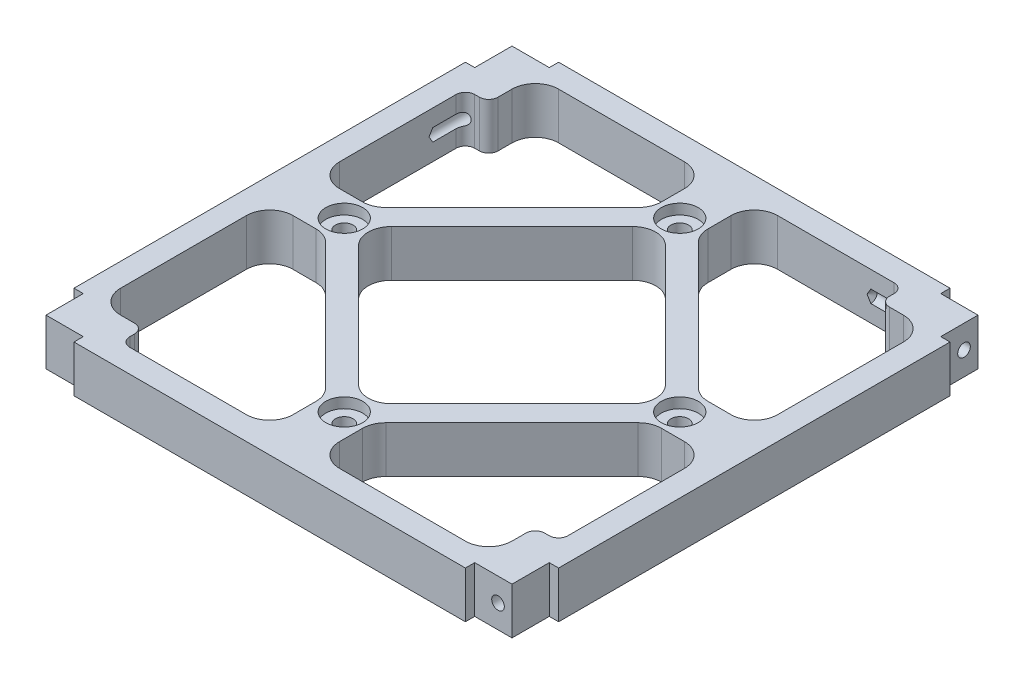
SolidWorks part; units mm, degrees
ref_plane "Front Plane" through (0, 0, 0) normal (0, 0, 1) x (1, 0, 0)
ref_plane "Top Plane" through (0, 0, 0) normal (0, 1, 0) x (1, 0, 0)
ref_plane "Right Plane" through (0, 0, 0) normal (1, 0, 0) x (0, 0, -1)
sketch "Sketch1" plane through (0, 0, 0) normal (0, 1, 0) x (1, 0, 0)
  line L0 (-42, 47) -> (-42, 37)
  line L1 (-52, 52) -> (52, 52)
  line L2 (-52, 52) -> (-52, -52)
  line L3 (-52, -52) -> (52, -52)
  line L4 (52, 52) -> (52, -52)
  line L5 (-47, 5) -> (-35, 5)
  line L6 (-35, 5) -> (-5, 35)
  line L7 (-5, 35) -> (-5, 47)
  line L8 (-5, 47) -> (-42, 47)
  line L9 (0, 0) -> (0, 76.3292) construction
  line L10 (0, 0) -> (-78.8537, 0) construction
  line L11 (0, 0) -> (-66.7994, 66.7994) construction
  line L12 (-32.9289, 0) -> (0, 32.9289)
  line L13 (0, 32.9289) -> (32.9289, 0)
  line L14 (32.9289, 0) -> (0, -32.9289)
  line L15 (0, -32.9289) -> (-32.9289, 0)
  line L16 (5, 47) -> (5, 35)
  line L17 (37, 47) -> (5, 47)
  line L18 (37, 42) -> (37, 47)
  line L19 (47, 42) -> (37, 42)
  line L20 (47, 5) -> (47, 42)
  line L21 (35, 5) -> (47, 5)
  line L22 (5, 35) -> (35, 5)
  line L23 (47, -5) -> (35, -5)
  line L24 (47, -37) -> (47, -5)
  line L25 (42, -37) -> (47, -37)
  line L26 (42, -47) -> (42, -37)
  line L27 (5, -47) -> (42, -47)
  line L28 (5, -35) -> (5, -47)
  line L29 (35, -5) -> (5, -35)
  line L30 (-5, -47) -> (-5, -35)
  line L31 (-42, 37) -> (-47, 37)
  line L32 (-47, 37) -> (-47, 5)
  line L33 (-37, -47) -> (-5, -47)
  line L34 (-37, -42) -> (-37, -47)
  line L35 (-47, -42) -> (-37, -42)
  line L36 (-47, -5) -> (-47, -42)
  line L37 (-35, -5) -> (-47, -5)
  line L38 (-5, -35) -> (-35, -5)
  point P36 (0.1996, 0.1996)
  point P45 (0, 0)
  dimension "D1" = 104
  dimension "D2" = 5
  dimension "D3" = 5
  dimension "D4" = 5
  dimension "D5" = 5
  dimension "D6" = 5
  dimension "D7" = 12
  dimension "D8" = 10
  dimension "D9" = 10
  dimension "D10" = 4
extrude "Boss-Extrude1" add sketch "Sketch1" along normal blind 10
fillet "Fillet1" radius 5 24 edges at (32.9289, 5, 0) (0, 5, 32.9289) (-32.9289, 5, 0) (0, 5, -32.9289) (-5, 5, -47) (-5, 5, -35) (-35, 5, -5) (-47, 5, 42) (-47, 5, 5) (-35, 5, 5) (-5, 5, 35) (-5, 5, 47) (42, 5, 47) (47, 5, 5) (35, 5, 5) (5, 5, 35) (5, 5, 47) (47, 5, -42) (47, 5, -5) (35, 5, -5) (5, 5, -35) (5, 5, -47) (-42, 5, -47) (-47, 5, -5)
sketch "Sketch2" plane through (0, 10, 0) normal (0, 1, 0) x (1, 0, 0)
  line L0 (-52, 52) -> (-42, 52)
  line L1 (52, 52) -> (-52, 52) construction
  line L2 (-42, 52) -> (-42, 50)
  line L3 (-42, 50) -> (-50, 50)
  line L4 (-50, 50) -> (-50, 42)
  line L5 (-50, 42) -> (-52, 42)
  line L6 (-52, 52) -> (-52, -52) construction
  line L7 (-52, 42) -> (-52, 52)
  dimension "D1" = 2
  dimension "D2" = 10
extrude "Cut-Extrude1" cut sketch "Sketch2" against normal through all
ref_axis "Axis1" through (0, 10.5, 0) along (0, -1, 0)
pattern_circular "CirPattern1" count 4 over 360 about axis through (0, 10.5, 0) along (0, -1, 0) of "Cut-Extrude1"
hole_wizard "CBORE for #6 Binding Head Machine Screw1" positions "Sketch3" profile "Sketch5" counterbore size "#6" standard "ANSI Inch" end condition through all
sketch "Sketch3" plane through (0, 10, 0) normal (0, 1, 0) x (1, 0, 0)
  line L2 (0, 36) -> (36, 0)
  line L3 (-36, 0) -> (0, -36)
  line L4 (36, 0) -> (0, -36)
  line L6 (0, 0) -> (0, 48.9753) construction
  line L7 (0, 0) -> (-18.2924, 0) construction
  line L9 (-36, 0) -> (0, 36)
  line L11 (-3.5355, 29.3934) -> (-29.3934, 3.5355) construction
  point P0 (0, 36)
  point P199 (-36, 0)
  point P315 (0, -36)
  point P316 (36, 0)
  dimension "D1" = 36
sketch "Sketch5" plane through (0, 10, -36) normal (1, 0, 0) x (0, 0, 1)
  line L0 (0, 0) -> (0, 10)
  line L1 (0, 10) -> (1.8986, 10)
  line L3 (1.8986, 10) -> (1.8987, 2.2098)
  line L4 (1.8987, 2.2098) -> (3.9687, 2.2098)
  line L5 (3.9687, 2.2098) -> (3.9687, 0)
  line L7 (3.9687, 0) -> (0, 0)
  line L11 (0, -6.35) -> (0, 107.95) construction
  dimension "Thru Hole Dia." = 3.7973
  dimension "Thru Hole Depth" = 10
  dimension "C'Bore Dia." = 7.9375
  dimension "C'Bore Depth" = 2.2098
fillet "Fillet3" radius 2 8 edges at (-37, 5, 42) (-37, 5, 47) (42, 5, 37) (47, 5, 37) (37, 5, -42) (37, 5, -47) (-47, 5, -37) (-42, 5, -37)
hole_wizard "#6-32 Tapped Hole1" positions "Sketch6" profile "Sketch9" tap size "#6-32" standard "ANSI Inch"
sketch "Sketch6" plane through (50, 0, 0) normal (1, 0, 0) x (0, 0, -1)
  line L2 (42, 10) -> (52, 0)
  point P0 (47, 5)
  point P13 (47, 5)
sketch "Sketch9" plane through (50, 5, -47) normal (0, 1, 0) x (0, 0, -1)
  line L0 (0, 0) -> (0, 20.8127)
  line L1 (0, 20.8127) -> (1.3525, 20)
  line L2 (1.3525, 20) -> (1.3525, 0)
  line L5 (1.3525, 0) -> (0, 0)
  line L10 (0, 20.8127) -> (-1.3525, 20) construction
  line L11 (0, -6.35) -> (0, 107.95) construction
  dimension "Tap Drill Dia." = 2.7051
  dimension "Tap Drill Depth" = 20
  dimension "Drill Angle" = 118
cosmetic thread "Hole Thread1" parameters "D1"=7.01, "D2"=3.5052
pattern_circular "CirPattern5" count 4 over 360 about axis through (0, 10.5, 0) along (0, -1, 0) of "#6-32 Tapped Hole1"
